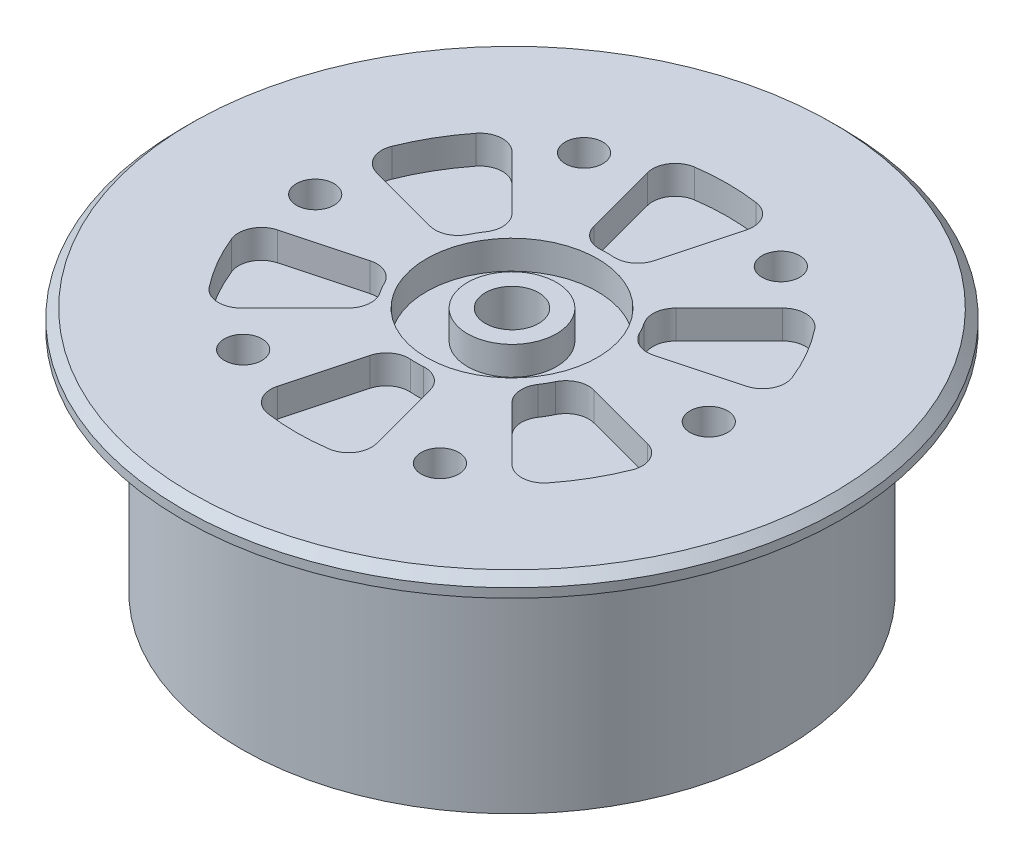
SolidWorks part; units mm, degrees
ref_plane "前视基准面" through (0, 0, 0) normal (0, 0, 1) x (1, 0, 0)
ref_plane "上视基准面" through (0, 0, 0) normal (0, 1, 0) x (1, 0, 0)
ref_plane "右视基准面" through (0, 0, 0) normal (1, 0, 0) x (0, 0, -1)
sketch "草图1" plane through (0, 0, 0) normal (0, 1, 0) x (1, 0, 0)
  circle A0 centre (0, 0) radius 28.9
  dimension "D1" = 57.8
extrude "凸台-拉伸1" add sketch "草图1" along normal blind 1.6 contours A0
chamfer "倒角1" distance 0.8 angle 45 1 edges at (0, 1.6, 28.9)
sketch "草图2" plane through (0, 0, 0) normal (0, -1, 0) x (1, 0, 0)
  circle A0 centre (0, 0) radius 23.75
  dimension "D1" = 47.5
extrude "凸台-拉伸2" add sketch "草图2" along normal blind 20 contours A0
sketch "草图3" plane through (0, 1.6, 0) normal (0, 1, 0) x (1, 0, 0)
  line L0 (0, 0) -> (50000, 0) construction
  line L1 (0, 0) -> (0, 50000) construction
  line L2 (0, 0) -> (43301.2702, 25000) construction
  line L3 (0, 0) -> (25000, 43301.2702) construction
  line L4 (0, 0) -> (43301.2702, -25000) construction
  line L5 (0, 0) -> (25000, -43301.2702) construction
  line L6 (-2.6283, 9.8089) -> (-4.3433, 16.2094)
  line L7 (2.6283, 9.8089) -> (4.3433, 16.2094)
  line L8 (9.8089, 2.6283) -> (16.2094, 4.3433)
  line L9 (7.1806, 7.1806) -> (11.8661, 11.8661)
  line L10 (7.1806, -7.1806) -> (11.8661, -11.8661)
  line L11 (9.8089, -2.6283) -> (16.2094, -4.3433)
  line L12 (-2.6283, -9.8089) -> (-4.3433, -16.2094)
  line L13 (2.6283, -9.8089) -> (4.3433, -16.2094)
  line L14 (-9.8089, -2.6283) -> (-16.2094, -4.3433)
  line L15 (-7.1806, -7.1806) -> (-11.8661, -11.8661)
  line L16 (-7.1806, 7.1806) -> (-11.8661, 11.8661)
  line L17 (-9.8089, 2.6283) -> (-16.2094, 4.3433)
  circle A0 centre (0, 0) radius 17.25 construction
  circle A1 centre (0, 0) radius 7.5
  circle A3 centre (0, 0) radius 18.9 construction
  arc A4 (-2.6968, 18.7066) -> (2.6968, 18.7066) centre (0, 0) cw
  arc A5 (-0.5619, 8.3311) -> (0.5619, 8.3311) centre (0, 0) cw
  arc A6 (7.4959, 3.679) -> (9.8089, 2.6283) centre (9.2913, 4.5601) ccw
  arc A7 (-2.6968, 18.7066) -> (-4.3433, 16.2094) centre (-2.4115, 16.7271) ccw
  arc A8 (2.6968, 18.7066) -> (4.3433, 16.2094) centre (2.4115, 16.7271) cw
  arc A9 (0.5619, 8.3311) -> (2.6283, 9.8089) centre (0.6964, 10.3265) ccw
  arc A10 (-0.5619, 8.3311) -> (-2.6283, 9.8089) centre (-0.6964, 10.3265) cw
  arc A11 (17.5488, 7.0178) -> (16.2094, 4.3433) centre (15.6918, 6.2752) cw
  arc A12 (14.852, 11.6888) -> (17.5488, 7.0178) centre (0, 0) cw
  arc A13 (14.852, 11.6888) -> (11.8661, 11.8661) centre (13.2803, 10.4519) ccw
  arc A14 (6.934, 4.6521) -> (7.1806, 7.1806) centre (8.5948, 5.7664) cw
  arc A15 (6.934, 4.6521) -> (7.4959, 3.679) centre (0, 0) cw
  arc A16 (6.934, -4.6521) -> (7.1806, -7.1806) centre (8.5948, -5.7664) ccw
  arc A17 (14.852, -11.6888) -> (11.8661, -11.8661) centre (13.2803, -10.4519) cw
  arc A18 (17.5488, -7.0178) -> (14.852, -11.6888) centre (0, 0) cw
  arc A19 (17.5488, -7.0178) -> (16.2094, -4.3433) centre (15.6918, -6.2752) ccw
  arc A20 (7.4959, -3.679) -> (9.8089, -2.6283) centre (9.2913, -4.5601) cw
  arc A21 (7.4959, -3.679) -> (6.934, -4.6521) centre (0, 0) cw
  arc A22 (-0.5619, -8.3311) -> (-2.6283, -9.8089) centre (-0.6964, -10.3265) ccw
  arc A23 (-2.6968, -18.7066) -> (-4.3433, -16.2094) centre (-2.4115, -16.7271) cw
  arc A24 (2.6968, -18.7066) -> (-2.6968, -18.7066) centre (0, 0) cw
  arc A25 (2.6968, -18.7066) -> (4.3433, -16.2094) centre (2.4115, -16.7271) ccw
  arc A26 (0.5619, -8.3311) -> (2.6283, -9.8089) centre (0.6964, -10.3265) cw
  arc A27 (0.5619, -8.3311) -> (-0.5619, -8.3311) centre (0, 0) cw
  arc A28 (-7.4959, -3.679) -> (-9.8089, -2.6283) centre (-9.2913, -4.5601) ccw
  arc A29 (-17.5488, -7.0178) -> (-16.2094, -4.3433) centre (-15.6918, -6.2752) cw
  arc A30 (-14.852, -11.6888) -> (-17.5488, -7.0178) centre (0, 0) cw
  arc A31 (-14.852, -11.6888) -> (-11.8661, -11.8661) centre (-13.2803, -10.4519) ccw
  arc A32 (-6.934, -4.6521) -> (-7.1806, -7.1806) centre (-8.5948, -5.7664) cw
  arc A33 (-6.934, -4.6521) -> (-7.4959, -3.679) centre (0, 0) cw
  arc A34 (-6.934, 4.6521) -> (-7.1806, 7.1806) centre (-8.5948, 5.7664) ccw
  arc A35 (-14.852, 11.6888) -> (-11.8661, 11.8661) centre (-13.2803, 10.4519) cw
  arc A36 (-17.5488, 7.0178) -> (-14.852, 11.6888) centre (0, 0) cw
  arc A37 (-17.5488, 7.0178) -> (-16.2094, 4.3433) centre (-15.6918, 6.2752) ccw
  arc A38 (-7.4959, 3.679) -> (-9.8089, 2.6283) centre (-9.2913, 4.5601) cw
  arc A39 (-7.4959, 3.679) -> (-6.934, 4.6521) centre (0, 0) cw
  point P16 (-17.25, 0)
  point P17 (-8.625, 14.9389)
  point P18 (8.625, 14.9389)
  point P19 (17.25, 0)
  point P20 (8.625, -14.9389)
  point P21 (-8.625, -14.9389)
  point P31 (-4.8917, 18.256)
  point P99 (0, 0)
  dimension "D5" = 34.5
  dimension "D6" = 15
  dimension "D7" = 1.65
  dimension "D8" = 8.35
  dimension "D9" = 2
  dimension "D1" = 30
  dimension "D2" = 30
  dimension "D3" = 30
  dimension "D4" = 30
  dimension "D10" = 15
  dimension "D11" = 15
  dimension "D12" = 6
hole_wizard "M4 螺纹孔的螺纹孔钻头1" positions "草图4" profile "草图5" hole size "M4" standard "GB"
sketch "草图4" plane through (0, 1.6, 0) normal (0, 1, 0) x (1, 0, 0)
  point P0 (-17.25, 0)
  point P3 (-8.625, 14.9389)
  point P6 (8.625, 14.9389)
  point P9 (17.25, 0)
  point P12 (8.625, -14.9389)
  point P15 (-8.625, -14.9389)
sketch "草图5" plane through (-17.25, 1.6, 0) normal (1, 0, 0) x (0, 0, 1)
  line L0 (0, 0) -> (0, 10)
  line L1 (0, 10) -> (1.65, 9.0086)
  line L2 (1.65, 9.0086) -> (1.65, 0)
  line L5 (1.65, 0) -> (0, 0)
  line L10 (0, 10) -> (-1.65, 9.0086) construction
  line L11 (0, -6.35) -> (0, 107.95) construction
  dimension "孔直径" = 3.3
  dimension "孔深度" = 10
  dimension "导头角度" = 118
extrude "切除-拉伸1" cut sketch "草图3" against normal blind 2.5 contours A1 | L7 A8 A4 A7 L6 A10 A5 A9 | L16 A35 A36 A37 L17 A38 A39 A34 | L8 A11 A12 A13 L9 A14 A15 A6 | L10 A17 A18 A19 L11 A20 A21 A16 | L12 A23 A24 A25 L13 A26 A27 A22 | L14 A29 A30 A31 L15 A32 A33 A28
sketch "草图7" plane through (0, -0.9, 0) normal (0, 1, 0) x (1, 0, 0)
  circle A0 centre (0, 0) radius 3.9
  point P2 (0, 0)
  dimension "D1" = 7.8
extrude "凸台-拉伸3" add sketch "草图7" along normal blind 2.5 contours A0
sketch "草图8" plane through (0, 1.6, 0) normal (0, 1, 0) x (1, 0, 0)
  circle A0 centre (0, 0) radius 2.34
  dimension "D1" = 4.68
extrude "切除-拉伸2" cut sketch "草图8" against normal blind 10 contours A0
